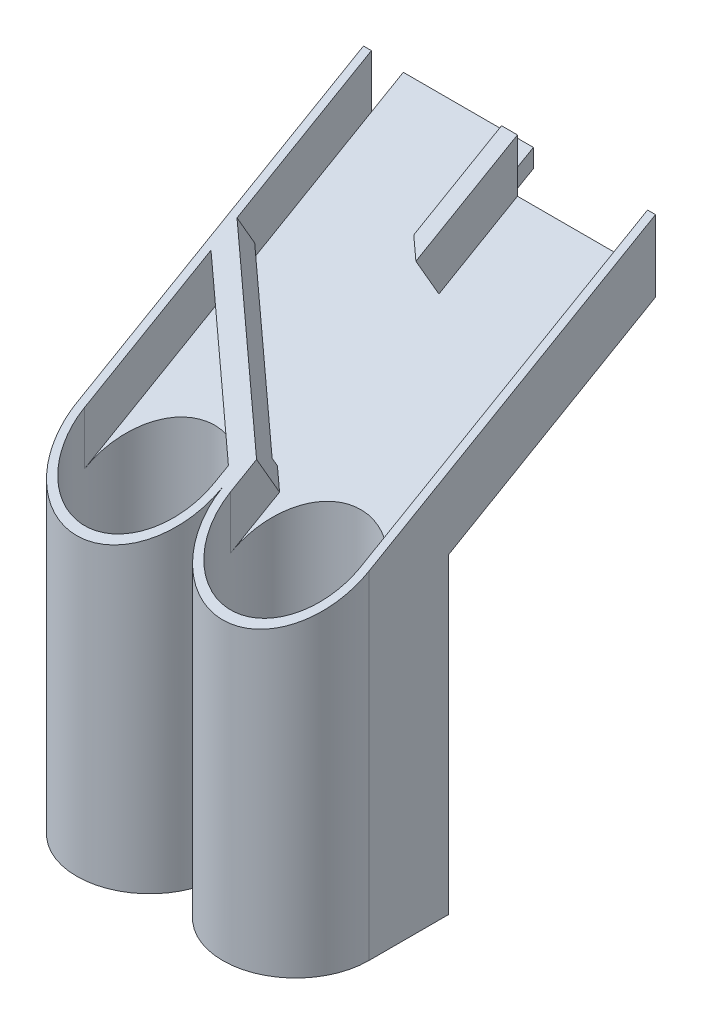
SolidWorks part; units mm, degrees
ref_plane "Front Plane" through (0, 0, 0) normal (0, 0, 1) x (1, 0, 0)
ref_plane "Top Plane" through (0, 0, 0) normal (0, 1, 0) x (1, 0, 0)
ref_plane "Right Plane" through (0, 0, 0) normal (1, 0, 0) x (0, 0, -1)
sketch "Sketch6" plane through (0, 0, 0) normal (0, 1, 0) x (1, 0, 0)
  line L0 (-27.5, 0) -> (-27.5, 120)
  line L1 (-27.5, 120) -> (27.5, 120)
  line L2 (27.5, 120) -> (27.5, 0)
  line L3 (0, 0) -> (0, 120) construction
  arc A0 (-27.5, 0) -> (27.5, 0) centre (0, 0) ccw
  dimension "D2" = 55
  dimension "D1" = 120
extrude "Boss-Extrude2" add sketch "Sketch6" along normal blind 300
sketch "Sketch7" plane through (0, 0, 0) normal (1, 0, 0) x (0, 0, -1)
  line L0 (120, 300) -> (0, 230.718)
  line L3 (-27.5, 300) -> (120, 300)
  line L4 (-27.5, 230.718) -> (-27.5, 300)
  line L5 (-27.5, 5) -> (0, 5) construction
  line L6 (0, 300) -> (0, 0) construction
  line L7 (120, 300) -> (120, 0) construction
  line L8 (0, 300) -> (120, 300) construction
  line L9 (-27.5, 300) -> (-27.5, 0) construction
  line L10 (0, 230.718) -> (-27.5, 230.718)
  dimension "D1" = 30
  dimension "D2" = 5
extrude "Cut-Extrude3" cut sketch "Sketch7" against normal through all both and the other way through all
sketch "Sketch9" plane through (0, 0, 0) normal (0, 1, 0) x (1, 0, 0)
  circle A0 centre (0, 0) radius 24.5
  dimension "D1" = 49
extrude "Cut-Extrude4" cut sketch "Sketch9" along normal through all
sketch "Sketch10" plane through (0, 0, 0) normal (0, 1, 0) x (1, 0, 0)
  line L0 (-24.5, 0) -> (-24.5, 120)
  line L1 (24.5, 0) -> (24.5, 120)
  line L2 (-24.5, 120) -> (-27.5, 120)
  line L3 (27.5, 0) -> (27.5, 120)
  line L4 (27.5, 120) -> (-27.5, 120)
  line L5 (-27.5, 120) -> (-27.5, 0)
  line L6 (27.5, 0) -> (27.5, 120)
  line L7 (27.5, 120) -> (24.5, 120)
  line L8 (-27.5, 120) -> (-27.5, 0)
  line L14 (24.5, 0) -> (27.5, 0)
  line L16 (-27.5, 0) -> (-24.5, 0)
  circle A0 centre (0, 0) radius 24.5 construction
  arc A1 (24.5, 0) -> (-24.5, 0) centre (0, 0) ccw
  arc A3 (-24.5, 0) -> (24.5, 0) centre (0, 0) ccw
  arc A4 (-27.5, 0) -> (27.5, 0) centre (0, 0) ccw construction
  arc A6 (-27.5, 0) -> (27.5, 0) centre (0, 0) ccw
  dimension "D1" = 0
extrude "Boss-Extrude3" add sketch "Sketch10" along normal blind 20 from surface starting at face at (0, 256.1695, -44.0833)
sketch "Sketch11" plane through (0, 0, 0) normal (0, 1, 0) x (1, 0, 0)
  line L0 (0, 0) -> (0, 79.0757) construction
  line L1 (-24.5, 120) -> (-24.5, 108)
  line L2 (-24.5, 108) -> (-27.5, 108)
  line L3 (-27.5, 120) -> (-27.5, 0) construction
  line L4 (-27.5, 108) -> (-27.5, 120)
  line L5 (-27.5, 120) -> (-24.5, 120)
  line L6 (24.5, 120) -> (-24.5, 120) construction
  line L7 (27.5, 120) -> (24.5, 120)
  line L8 (27.5, 108) -> (27.5, 120)
  line L9 (24.5, 108) -> (27.5, 108)
  line L10 (24.5, 120) -> (24.5, 108)
  dimension "D1" = 49
  dimension "D2" = 12
extrude "Cut-Extrude6" cut sketch "Sketch11" along normal through all
mirror "Mirror1" about plane through (27.5, 300, -120) normal (-1, 0, 0) of bodies 108
sketch "Sketch12" plane through (0, 188.0385, 108.5641) normal (0, 0.866, 0.5) x (1, 0, 0)
  line L0 (24.5, 253.923) -> (-24.5, 253.923) construction
  line L1 (-24.5, 191.6032) -> (24.5, 142.6032)
  line L2 (-24.5, 125.359) -> (-24.5, 250.0666) construction
  line L3 (24.5, 250.0666) -> (24.5, 125.359) construction
  line L4 (-24.5, 191.6032) -> (-24.5, 180.2895)
  line L5 (-24.5, 115.359) -> (-24.5, 240.0666) construction
  line L6 (-24.5, 180.2895) -> (24.5, 131.2895)
  line L7 (24.5, 131.2895) -> (24.5, 142.6032)
  line L8 (0, 198.923) -> (-24.5, 198.923) construction
  line L9 (0, 198.923) -> (24.5, 198.923) construction
  circle A0 centre (0, 198.923) radius 22.5 construction
  dimension "D1" = 45
  dimension "D2" = 55
  dimension "D3" = 8
  dimension "D4" = 45
extrude "Boss-Extrude4" add sketch "Sketch12" against normal offset from surface (13.3205 mm away) 4 up to face at (0, 276.9541, -80.0833)
sketch "Sketch13" plane through (0, 188.0385, 108.5641) normal (0, 0.866, 0.5) x (1, 0, 0)
  line L0 (24.5, 142.6032) -> (30.5, 136.6032)
  line L1 (30.5, 240.0666) -> (30.5, 115.359) construction
  line L2 (30.5, 136.6032) -> (30.5, 205.8997)
  line L3 (30.5, 250.0666) -> (30.5, 125.359) construction
  line L4 (30.5, 205.8997) -> (24.5, 211.8997)
  line L5 (24.5, 240.0666) -> (24.5, 115.359) construction
  line L6 (24.5, 211.8997) -> (24.5, 142.6032)
  line L7 (24.5, 142.6032) -> (-24.5, 191.6032) construction
  circle A0 centre (24.5, 177.2515) radius 24.5 construction
  dimension "D1" = 49
extrude "Cut-Extrude8" cut sketch "Sketch13" against normal up to surface (17.3205 mm away) up to face at (0, 276.9541, -80.0833)
ref_plane "Plane1" through (0, 230.718, 0) normal (0, 1, 0) x (1, 0, 0)
sketch "Sketch14" plane through (0, 230.718, 0) normal (0, -1, 0) x (1, 0, 0)
  circle A0 centre (0, 0) radius 24.5
  circle A1 centre (0, 0) radius 24.5 construction
extrude "Boss-Extrude5" add sketch "Sketch14" along normal up to surface (230.718 mm away) from offset 63 up to face at (0, 0, 24.5)
sketch "Sketch15" plane through (0, 230.718, 0) normal (0, 1, 0) x (1, 0, 0)
  circle A0 centre (55, 0) radius 24.5
  arc A1 (79.5, 0) -> (30.5, 0) centre (55, 0) ccw construction
extrude "Boss-Extrude6" add sketch "Sketch15" against normal up to surface (230.718 mm away) from offset 105 up to face at (27.5, 0, -82.5385) offset against normal yes
sketch "Sketch16" plane through (0, 0, 0) normal (0, -1, 0) x (1, 0, 0)
  line L11 (-27.5, -108) -> (-24.5, -108)
  line L12 (-24.5, -108) -> (-24.5, -120)
  line L13 (-24.5, -120) -> (24.5, -120)
  line L14 (24.5, -120) -> (24.5, -108)
  line L15 (24.5, -108) -> (30.5, -108)
  line L16 (30.5, -108) -> (30.5, -120)
  line L17 (30.5, -120) -> (79.5, -120)
  line L18 (79.5, -120) -> (79.5, -108)
  line L19 (79.5, -108) -> (82.5, -108)
  line L20 (82.5, -108) -> (82.5, 0)
  line L21 (-27.5, 0) -> (-27.5, -108)
  line L22 (-27.5, -108) -> (-24.5, -108)
  line L23 (-24.5, -108) -> (-24.5, -120)
  line L24 (-24.5, -120) -> (24.5, -120)
  line L25 (24.5, -120) -> (24.5, -108)
  line L26 (24.5, -108) -> (30.5, -108)
  line L27 (30.5, -108) -> (30.5, -120)
  line L28 (30.5, -120) -> (79.5, -120)
  line L29 (79.5, -120) -> (79.5, -108)
  line L30 (79.5, -108) -> (82.5, -108)
  line L31 (82.5, -108) -> (82.5, 0)
  line L32 (-27.5, 0) -> (-27.5, -108)
  arc A2 (82.5, 0) -> (27.5, 0) centre (55, 0) ccw
  arc A3 (27.5, 0) -> (-27.5, 0) centre (0, 0) ccw
  arc A4 (82.5, 0) -> (27.5, 0) centre (55, 0) ccw
  arc A5 (27.5, 0) -> (-27.5, 0) centre (0, 0) ccw
  dimension "D1" = 0
extrude "Cut-Extrude9" cut sketch "Sketch16" against normal offset from surface (123.718 mm away) 2 up to face at (55, 125.718, 24.5)
sketch "Sketch17" plane through (0, 230.718, 0) normal (0, 1, 0) x (1, 0, 0)
  line L0 (79.5, 108) -> (79.5, 120) construction
  line L1 (30.5, 120) -> (79.5, 120)
  line L2 (30.5, 120) -> (30.5, 108)
  line L3 (30.5, 108) -> (79.5, 108)
  line L4 (79.5, 120) -> (79.5, 108)
extrude "Cut-Extrude10" cut sketch "Sketch17" against normal through all both and the other way through all
sketch "Sketch18" plane through (82.5, 0, 0) normal (1, 0, 0) x (0, 0, -1)
  line L0 (30, 123.718) -> (30, 241.1103)
  line L1 (108, 123.718) -> (0, 123.718) construction
  line L2 (30, 241.1103) -> (120, 293.0718)
  line L3 (120, 300) -> (120, 123.718) construction
  line L4 (120, 300) -> (108, 293.0718) construction
  line L6 (30, 123.718) -> (120, 123.718)
  line L7 (120, 123.718) -> (120, 293.0718)
  dimension "D1" = 6
  dimension "D2" = 30
extrude "Cut-Extrude11" cut sketch "Sketch18" against normal through all
